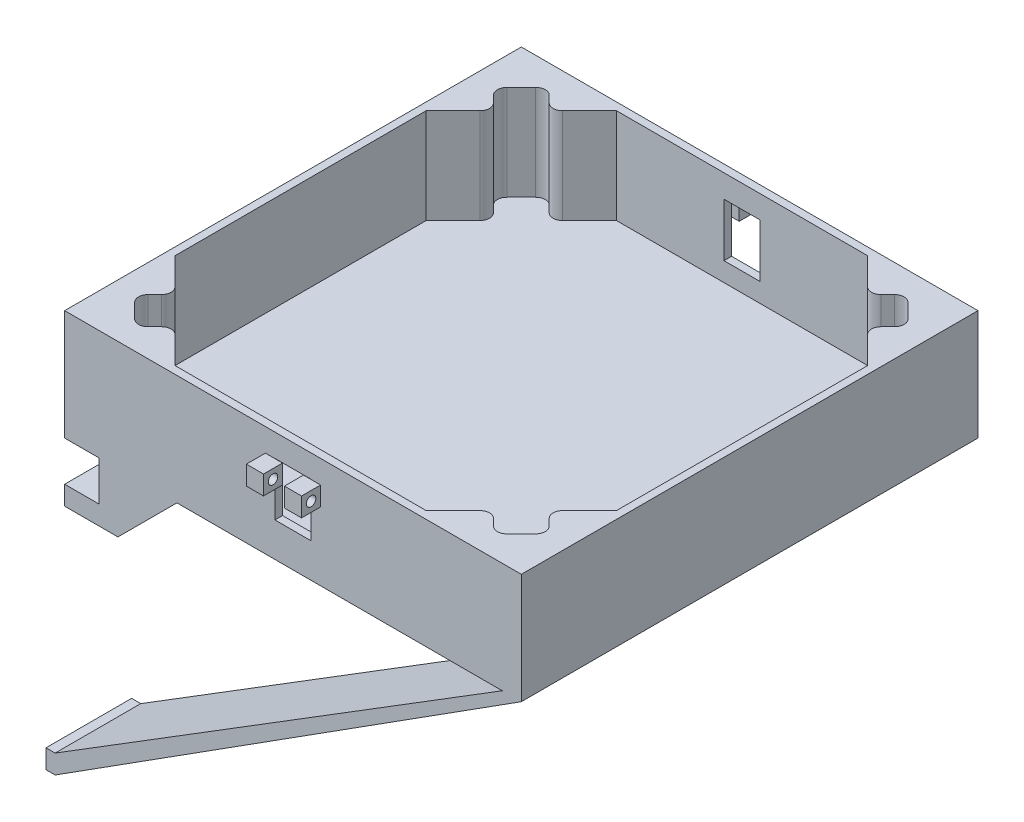
SolidWorks part; units mm, degrees
ref_plane "Płaszczyzna przednia" through (0, 0, 0) normal (0, 0, 1) x (1, 0, 0)
ref_plane "Płaszczyzna górna" through (0, 0, 0) normal (0, 1, 0) x (1, 0, 0)
ref_plane "Płaszczyzna prawa" through (0, 0, 0) normal (1, 0, 0) x (0, 0, -1)
sketch "Szkic1" plane through (0, 0, 0) normal (0, 1, 0) x (1, 0, 0)
  line L1 (-120, -120) -> (120, -120)
  line L2 (-120, -120) -> (-120, 120)
  line L3 (-120, 120) -> (120, 120)
  line L4 (120, -120) -> (120, 120)
  line L5 (-120, -120) -> (120, 120) construction
  line L6 (-120, 120) -> (120, -120) construction
  point P0 (0, 0)
  dimension "D1" = 240
  dimension "D2" = 240
extrude "Dodanie-wyciągnięcie1" add sketch "Szkic1" along normal blind 8
sketch "Szkic2" plane through (0, 8, 0) normal (0, 1, 0) x (1, 0, 0)
  line L1 (-120, -120) -> (120, -120)
  line L2 (-120, -120) -> (-120, 120)
  line L3 (-120, 120) -> (120, 120)
  line L4 (120, -120) -> (120, 120)
  line L5 (-120, -120) -> (120, 120) construction
  line L6 (-120, 120) -> (120, -120) construction
  line L7 (-116, -116) -> (116, -116)
  line L8 (-116, -116) -> (-116, 116)
  line L9 (-116, 116) -> (116, 116)
  line L10 (116, -116) -> (116, 116)
  line L11 (-116, -116) -> (116, 116) construction
  line L12 (-116, 116) -> (116, -116) construction
  point P0 (0, 0)
  point P7 (0, 0)
  dimension "D1" = 4
extrude "Dodanie-wyciągnięcie2" add sketch "Szkic2" along normal blind 50
sketch "Szkic4" plane through (0, 8, 0) normal (0, 1, 0) x (1, 0, 0)
  circle A0 centre (0, 0) radius 17
  circle A1 centre (0, 0) radius 40
  circle A2 centre (0, 0) radius 44
  circle A3 centre (0, 0) radius 80
  circle A4 centre (0, 0) radius 84
  circle A5 centre (0, 0) radius 14
  dimension "D1" = 34
  dimension "D2" = 80
  dimension "D3" = 88
  dimension "D4" = 160
  dimension "D5" = 168
  dimension "D6" = 28
sketch "Szkic11" plane through (0, 8, 0) normal (0, 1, 0) x (1, 0, 0)
  line L0 (-116, 116) -> (-66, 116)
  line L1 (116, 116) -> (-116, 116) construction
  line L2 (-66, 116) -> (-83.6777, 98.3223)
  line L3 (-83.6777, 98.3223) -> (-94.2843, 108.9289)
  line L4 (-94.2843, 108.9289) -> (-108.9289, 94.2843)
  line L5 (-108.9289, 94.2843) -> (-98.3223, 83.6777)
  line L6 (-98.3223, 83.6777) -> (-116, 66)
  line L7 (-116, 116) -> (-116, -116) construction
  line L8 (-116, 66) -> (-116, 116)
  dimension "D1" = 50
  dimension "D2" = 50
  dimension "D3" = 25
  dimension "D4" = 25
  dimension "D5" = 15
extrude "Dodanie-wyciągnięcie6" add sketch "Szkic11" along normal blind 50
fillet "Zaokrąglenie1" radius 5 4 edges at (-98.3223, 33, -83.6777) (-108.9289, 33, -94.2843) (-94.2843, 33, -108.9289) (-83.6777, 33, -98.3223)
ref_axis "Oś1" through (0, -2.9, 0) along (0, 1, 0)
pattern_circular "Szyk kołowy1" count 4 every 90 about axis through (0, -2.9, 0) along (0, 1, 0) of "Zaokrąglenie1", "Dodanie-wyciągnięcie6"
sketch "Szkic12" plane through (0, 0, -120) normal (0, 0, -1) x (-1, 0, 0)
  line L0 (0, 0) -> (0, 32) construction
  line L2 (-9.5, 46) -> (9.5, 46)
  line L3 (-9.5, 46) -> (-9.5, 18)
  line L4 (-9.5, 18) -> (9.5, 18)
  line L5 (9.5, 46) -> (9.5, 18)
  line L6 (-9.5, 46) -> (9.5, 18) construction
  line L7 (-9.5, 18) -> (9.5, 46) construction
  dimension "D1" = 32
  dimension "D2" = 28
  dimension "D3" = 19
extrude "Wytnij-wyciągnięcie3" cut sketch "Szkic12" against normal through all
sketch "Szkic15" plane through (0, 0, 120) normal (0, 0, 1) x (1, 0, 0)
  line L0 (0, -31.9) -> (0, 31.9) construction
  line L1 (9.5, 45.9) -> (14.5, 45.9)
  line L2 (9.5, 45.9) -> (9.5, 35.9) construction
  line L3 (9.5, 35.9) -> (14.5, 35.9)
  line L4 (14.5, 45.9) -> (14.5, 35.9)
  line L5 (-14.5, 45.9) -> (-14.5, 35.9)
  line L6 (-9.5, 35.9) -> (-14.5, 35.9)
  line L7 (-9.5, 45.9) -> (-9.5, 35.9) construction
  line L8 (-9.5, 45.9) -> (-14.5, 45.9)
  line L9 (-5.5, 45.9) -> (-9.5, 45.9)
  line L10 (9.5, 35.9) -> (5.5, 35.9)
  line L11 (5.5, 35.9) -> (5.5, 45.9)
  line L13 (5.5, 45.9) -> (9.5, 45.9)
  line L14 (-5.5, 35.9) -> (-5.5, 45.9)
  line L15 (-9.5, 35.9) -> (-5.5, 35.9)
  line L16 (-9.5, 46) -> (9.5, 46) construction
  dimension "D1" = 10
  dimension "D2" = 5
  dimension "D3" = 4
  dimension "D4" = 0.1
extrude "Dodanie-wyciągnięcie7" add sketch "Szkic15" along normal blind 10
sketch "Szkic16" plane through (14.5, 0, 0) normal (1, 0, 0) x (0, 0, -1)
  circle A0 centre (-125, 41) radius 2.5
  dimension "D1" = 5
extrude "Wytnij-wyciągnięcie4" cut sketch "Szkic16" against normal through all
mirror "Lustro1" about plane through (0, 0, 0) normal (0, 0, 1) of "Dodanie-wyciągnięcie7", "Wytnij-wyciągnięcie4"
extrude "Wytnij-wyciągnięcie1" [suppressed] cut sketch "Szkic4" against normal blind 2 contours A4 A3 | A2 A1 | A0 A5
sketch "Szkic5" plane through (0, 0, 0) normal (0, -1, 0) x (1, 0, 0)
  line L0 (-102, 120) -> (-102, -120)
  line L1 (-120, 120) -> (120, 120) construction
  line L2 (120, -120) -> (-120, -120) construction
  line L3 (-102, -120) -> (-92, -120)
  line L4 (-92, -120) -> (-92, 120)
  line L5 (-92, 120) -> (-102, 120)
  line L6 (-120, -120) -> (-120, 120) construction
  dimension "D1" = 10
  dimension "D2" = 18
extrude "Dodanie-wyciągnięcie3" add sketch "Szkic5" along normal blind 21
sketch "Szkic6" plane through (0, -21, 0) normal (0, -1, 0) x (1, 0, 0)
  line L5 (-92, 120) -> (-120, 120)
  line L6 (-92, 120) -> (-92, -120)
  line L7 (-92, -120) -> (-120, -120)
  line L8 (-120, 120) -> (-120, -120)
extrude "Dodanie-wyciągnięcie4" add sketch "Szkic6" along normal blind 10
chamfer "Sfazowanie2" distance 31 angle 45 1 edges at (-92, 0, 0)
sketch "Szkic7" plane through (0, 0, 0) normal (0, -1, 0) x (1, 0, 0)
  line L0 (120, -120) -> (-61, -120) construction
  line L1 (120, 120) -> (110, 120)
  line L2 (120, 120) -> (120, -120)
  line L3 (120, -120) -> (110, -120)
  line L4 (110, 120) -> (110, -120)
  dimension "D1" = 10
ref_plane "Płaszczyzna2" through (-125, 0, 0) normal (-1, 0, 0) x (0, 0, 1)
sketch "Szkic8" plane through (-125, 0, 0) normal (-1, 0, 0) x (0, 0, 1)
  line L0 (0, 0) -> (0, -150.8545) construction
  line L1 (120, -21) -> (120, 0) construction
  line L2 (-120, -155.8545) -> (120, -155.8545)
  line L3 (-120, -155.8545) -> (-120, -145.8545)
  line L4 (-120, -145.8545) -> (120, -145.8545)
  line L5 (120, -155.8545) -> (120, -145.8545)
  line L6 (-120, -155.8545) -> (120, -145.8545) construction
  line L7 (-120, -145.8545) -> (120, -155.8545) construction
  dimension "D1" = 10
loft "Wyciągnięcie po profilach1" add profiles "Szkic8", "Szkic7" connector at (-125, -155.8545, -120) connector at (120, 0, -120)
sketch "Szkic9" plane through (120, 0, 0) normal (1, 0, 0) x (0, 0, -1)
  line L1 (75, 0) -> (-75, 0)
  line L2 (75, 0) -> (75, -155.8545)
  line L3 (75, -155.8545) -> (-75, -155.8545)
  line L4 (-75, 0) -> (-75, -155.8545)
  dimension "D1" = 150
extrude "Wytnij-wyciągnięcie2" cut sketch "Szkic9" against normal through all both and the other way through all
sketch "Szkic10" plane through (-125, 0, 0) normal (-1, 0, 0) x (0, 0, 1)
  line L0 (75, -155.8545) -> (120, -155.8545) construction
  line L1 (120, -145.8545) -> (75, -145.8545)
  line L2 (120, -145.8545) -> (120, -155.8545)
  line L3 (120, -155.8545) -> (75, -155.8545)
  line L4 (75, -145.8545) -> (75, -155.8545)
  line L5 (-75, -155.8545) -> (-120, -155.8545)
  line L6 (-75, -155.8545) -> (-75, -145.8545)
  line L7 (-75, -145.8545) -> (-120, -145.8545)
  line L8 (-120, -155.8545) -> (-120, -145.8545)
extrude "Dodanie-wyciągnięcie5" add sketch "Szkic10" along normal blind 4.8
